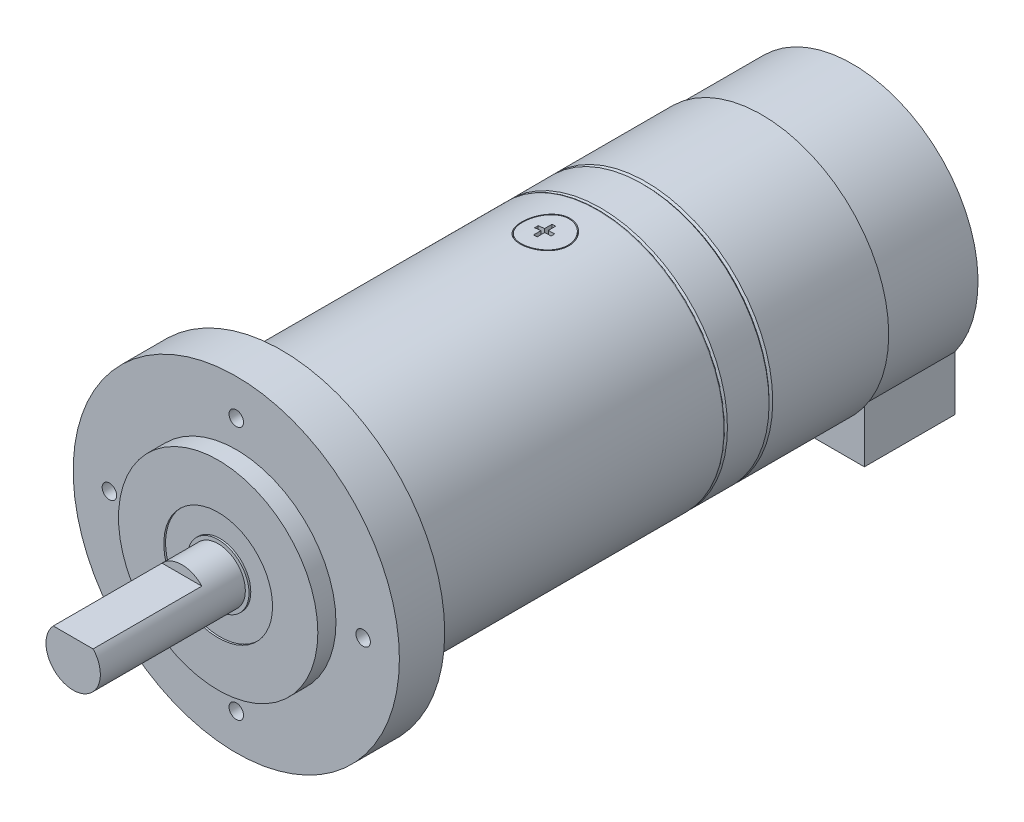
SolidWorks part; units mm, degrees
ref_plane "Front Plane" through (0, 0, 0) normal (0, 0, 1) x (1, 0, 0)
ref_plane "Top Plane" through (0, 0, 0) normal (0, 1, 0) x (1, 0, 0)
ref_plane "Right Plane" through (0, 0, 0) normal (1, 0, 0) x (0, 0, -1)
sketch "Sketch1" plane through (0, 0, 0) normal (0, 0, 1) x (1, 0, 0)
  circle A0 centre (0, 0) radius 18
  circle A1 centre (0, 0) radius 11
  dimension "D1" = 36
  dimension "D2" = 22
extrude "Boss-Extrude2" add sketch "Sketch1" against normal blind 5 contours A0
extrude "Boss-Extrude3" add sketch "Sketch1<4>" along normal blind 2 contours A1
sketch "Sketch1<4>" plane through (0, 0, 0) normal (0, 0, 1) x (1, 0, 0) same geometry as "Sketch1"
sketch "Sketch2" plane through (0, 0, 2) normal (0, 0, 1) x (1, 0, 0)
  circle A0 centre (0, 0) radius 3
  dimension "D1" = 6
extrude "Boss-Extrude4" add sketch "Sketch2" along normal blind 16 contours A0
sketch "Sketch3" plane through (0, 0, 18) normal (0, 0, 1) x (1, 0, 0)
  line L1 (-2.9161, 3.7933) -> (3.4469, 3.7933)
  line L2 (-2.9161, 3.7933) -> (-2.9161, 2.0435)
  line L3 (-2.9161, 2.0435) -> (3.4469, 2.0435)
  line L4 (3.4469, 3.7933) -> (3.4469, 2.0435)
extrude "Cut-Extrude1" cut sketch "Sketch3" against normal blind 12
sketch "Sketch4" plane through (0, 0, 2) normal (0, 0, 1) x (1, 0, 0)
  circle A0 centre (0, 0) radius 6
  circle A1 centre (0, 0) radius 3.4
  dimension "D1" = 12
  dimension "D2" = 6.8
extrude "Cut-Extrude2" cut sketch "Sketch4" against normal blind 0.2
sketch "Sketch5" plane through (0, 0, -5) normal (0, 0, -1) x (-1, 0, 0)
  circle A0 centre (0, 0) radius 14
  point P3 (0, 14)
  point P4 (-14, 0)
  point P5 (0, -14)
  point P6 (14, 0)
hole_wizard "Tap Drill for M2x0.4 Tap1" positions "3DSketch1" profile "Sketch6" hole size "M2x0.4" standard "ANSI Metric" end condition through all
sketch3d "3DSketch1"
  point P0 (0, 14, -5)
  point P3 (14, 0, -5)
  point P6 (0, -14, -5)
  point P9 (-14, 0, -5)
sketch "Sketch6" plane through (0, 14, -5) normal (1, 0, 0) x (0, 1, 0)
  line L0 (0, 0) -> (0, 23)
  line L1 (0, 23) -> (0.8, 23)
  line L2 (0.8, 23) -> (0.8, 0)
  line L5 (0.8, 0) -> (0, 0)
  line L11 (0, -6.35) -> (0, 107.95) construction
  dimension "Thru Hole Dia." = 1.6
  dimension "Thru Hole Depth" = 23
extrude "Boss-Extrude5" add sketch "Sketch5" along normal blind 35 contours A0
fillet "Fillet2" radius 0.2 1 edges at (-14, 0, -40)
sketch "Sketch7" plane through (0, 0, -40) normal (0, 0, -1) x (-1, 0, 0)
  circle A0 centre (0, 0) radius 14
extrude "Boss-Extrude6" add sketch "Sketch7" along normal blind 5
chamfer "Chamfer1" distance 0.2 angle 45 2 edges at (-14, 0, -45) (-14, 0, -40)
sketch "Sketch8" plane through (0, 0, -45) normal (0, 0, -1) x (-1, 0, 0)
  circle A0 centre (0, 0) radius 14
sketch "Sketch10" plane through (0, 0, -45) normal (0, 0, -1) x (-1, 0, 0)
  circle A0 centre (0, 0) radius 14
extrude "Boss-Extrude7" add sketch "Sketch10" along normal blind 13
chamfer "Chamfer2" distance 0.2 angle 45 1 edges at (-14, 0, -45)
sketch "Sketch11" plane through (0, 0, -58) normal (0, 0, -1) x (-1, 0, 0)
  line L2 (-11.3137, -8) -> (-11.3137, -14)
  line L3 (-11.3137, -14) -> (11.3137, -14)
  line L4 (11.3137, -8) -> (11.3137, -14)
  arc A0 (11.3137, -8) -> (-11.3137, -8) centre (0, 0) ccw
  circle A1 centre (0, 0) radius 18 construction
  dimension "D1" = 6
  dimension "D2" = 6
extrude "Boss-Extrude8" add sketch "Sketch11" along normal blind 10 separate body
ref_plane "Plane1" through (0, 14, 0) normal (0, 1, 0) x (1, 0, 0)
sketch "Sketch12" plane through (0, 14, 0) normal (0, 1, 0) x (1, 0, 0)
  circle A0 centre (-0.8303, 34.9357) radius 2.5
  circle A1 centre (-0.8303, 34.9357) radius 2.6
  dimension "D1" = 0.1
extrude "Cut-Extrude3" cut sketch "Sketch12" against normal blind 10.13
sketch "Sketch13" plane through (0, 14, 0) normal (0, 1, 0) x (1, 0, 0)
  line L0 (-0.7432, 35.174) -> (-0.0372, 35.174)
  line L1 (-1.8588, 34.7774) -> (-1.1577, 34.7774)
  line L2 (-1.8588, 34.7774) -> (-1.8588, 35.174)
  line L3 (-1.8588, 35.174) -> (-1.1577, 35.174)
  line L4 (-0.0372, 34.7774) -> (-0.0372, 35.174)
  line L5 (-1.1577, 33.9448) -> (-0.7432, 33.9448)
  line L6 (-1.1577, 33.9448) -> (-1.1577, 34.7774)
  line L7 (-1.1577, 35.9946) -> (-0.7432, 35.9946)
  line L8 (-0.7432, 33.9448) -> (-0.7432, 34.7774)
  line L9 (-0.7432, 34.7774) -> (-0.0372, 34.7774)
  line L10 (-1.1577, 35.174) -> (-1.1577, 35.9946)
  line L11 (-0.7432, 35.174) -> (-0.7432, 35.9946)
extrude "Cut-Extrude4" cut sketch "Sketch13" against normal blind 2
